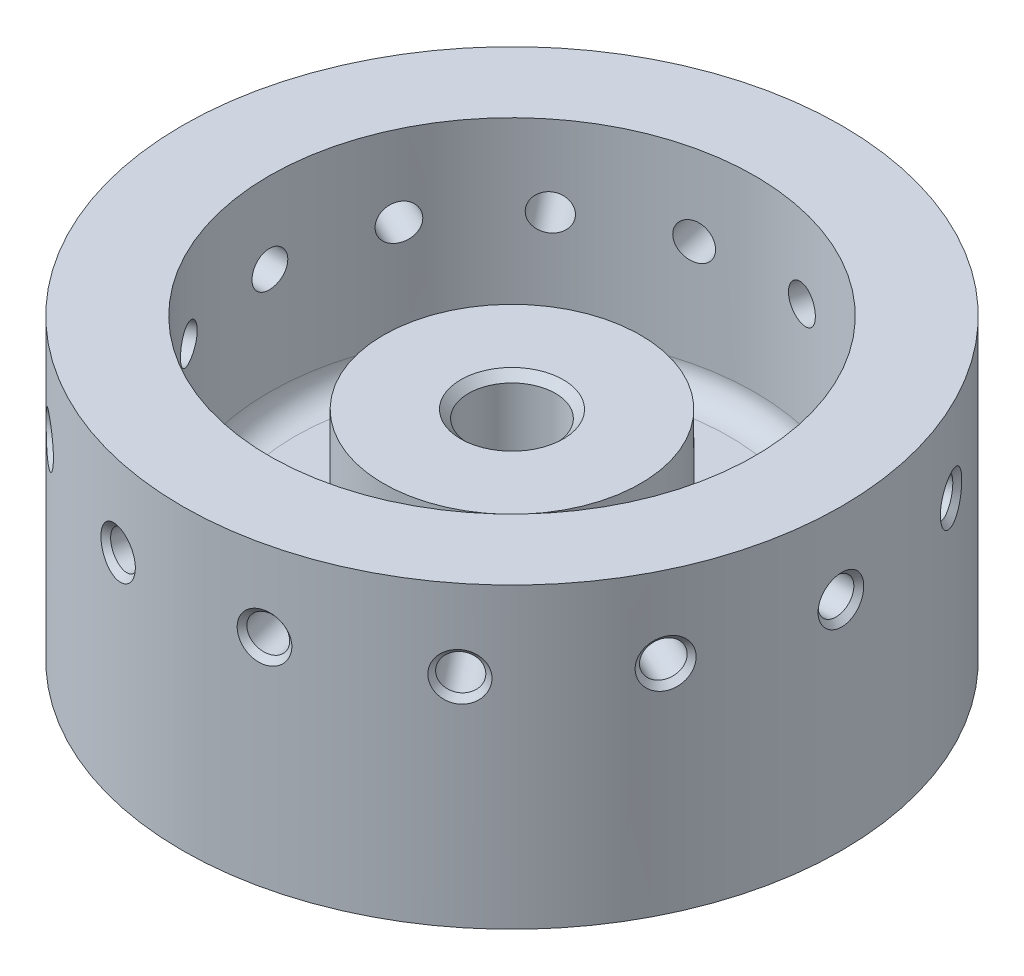
SolidWorks part; units mm, degrees
material "6061-T6 (SS)"
ref_plane "Front Plane" through (0, 0, 0) normal (0, 0, 1) x (1, 0, 0)
ref_plane "Top Plane" through (0, 0, 0) normal (0, 1, 0) x (1, 0, 0)
ref_plane "Right Plane" through (0, 0, 0) normal (1, 0, 0) x (0, 0, -1)
sketch "Sketch1" plane through (0, 0, 0) normal (0, 0, 1) x (1, 0, 0)
  line L0 (0, 0) -> (0, -61212.8675) construction
  line L1 (0, 0) -> (38.71, 0)
  line L2 (38.71, 0) -> (38.71, 35)
  line L3 (38.71, 35) -> (28.5, 35)
  line L4 (28.5, 35) -> (28.5, 10)
  line L5 (28.5, 10) -> (15.1, 10)
  line L6 (15.1, 10) -> (15.1, 25.5)
  line L7 (15.1, 25.5) -> (0, 25.5)
  line L8 (0, 25.5) -> (0, 0)
  dimension "D1" = 30.2
  dimension "D2" = 9.5
  dimension "D3" = 35
  dimension "D4" = 25
  dimension "D5" = 57
  dimension "D6" = 77.42
revolve "Revolve1" add sketch "Sketch1" angle 360 about L0
sketch "Sketch4" plane through (0, 25.5, 0) normal (0, 1, 0) x (1, 0, 0)
  point P0 (0, 0)
hole_wizard "M12 Tapped Hole1" positions "Sketch4" profile "Sketch5" tap size "M12" standard "ISO"
sketch "Sketch5" plane through (0, 25.5, 0) normal (1, 0, 0) x (0, 0, 1)
  line L0 (0, 0) -> (0, 23.0644)
  line L1 (0, 23.0644) -> (5.1, 20)
  line L2 (5.1, 20) -> (5.1, 0.925)
  line L3 (5.1, 0.925) -> (6.025, 0)
  line L5 (6.025, 0) -> (0, 0)
  line L6 (-5.1, 0.925) -> (-6.025, 0) construction
  line L10 (0, 23.0644) -> (-5.1, 20) construction
  line L11 (0, -6.35) -> (0, 107.95) construction
  dimension "Tap Drill Dia." = 10.2
  dimension "Tap Drill Depth" = 20
  dimension "Near C'Sink Dia." = 12.05
  dimension "Near C'Sink Angle" = 90
  dimension "Drill Angle" = 118
cosmetic thread "Hole Thread1"
fillet "Fillet1" radius 3 2 edges at (-28.5, 10, 0) (-15.1, 10, 0)
hole_wizard "M5 Tapped Hole1" positions "3DSketch1" profile "Sketch6" tap size "M5" standard "ISO" end condition up to next
sketch3d "3DSketch1"
  point P0 (-38.71, 25.5, 0)
  dimension "D1" = 9.5
sketch "Sketch6" plane through (-38.71, 25.5, 0) normal (0, 1, 0) x (0, 0, 1)
  line L0 (0, 0) -> (0, 10.21)
  line L1 (0, 10.21) -> (2.1, 10.21)
  line L2 (2.1, 10.21) -> (2.1, 0.675)
  line L3 (2.1, 0.675) -> (2.775, 0)
  line L5 (2.775, 0) -> (0, 0)
  line L6 (-2.1, 0.675) -> (-2.775, 0) construction
  line L11 (0, -6.35) -> (0, 107.95) construction
  dimension "Thru Tap Drill Dia." = 4.2
  dimension "Thru Tap Drill Depth" = 10.21
  dimension "Near C'Sink Dia." = 5.55
  dimension "Near C'Sink Angle" = 90
cosmetic thread "Hole Thread2"
pattern_circular "CirPattern1" count 14 over 360 about axis through (0, 0, 0) along (0, 1, 0) of "M5 Tapped Hole1" reverse direction yes
cosmetic thread "Hole Thread3"
cosmetic thread "Hole Thread4"
cosmetic thread "Hole Thread5"
cosmetic thread "Hole Thread6"
cosmetic thread "Hole Thread7"
cosmetic thread "Hole Thread8"
cosmetic thread "Hole Thread9"
cosmetic thread "Hole Thread10"
cosmetic thread "Hole Thread11"
cosmetic thread "Hole Thread12"
cosmetic thread "Hole Thread13"
cosmetic thread "Hole Thread14"
cosmetic thread "Hole Thread15"
